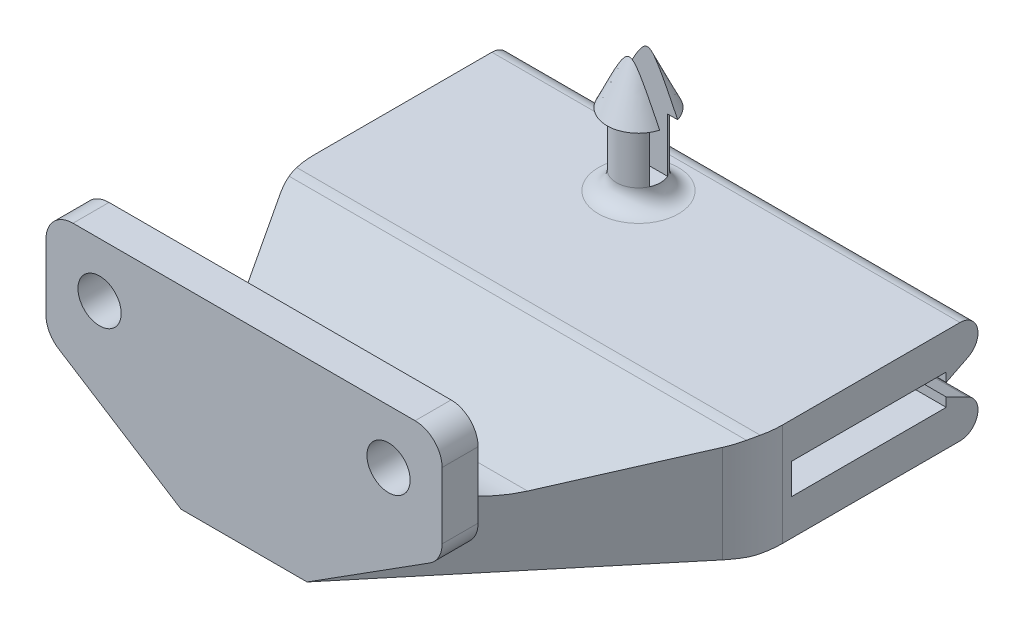
SolidWorks part; units mm, degrees
note: The reader was unsure of these and kept them because the rebuilt part matched: shared geometry of "Sketch5<3>".
ref_plane "Front Plane" through (0, 0, 0) normal (0, 0, 1) x (1, 0, 0)
ref_plane "Top Plane" through (0, 0, 0) normal (0, 1, 0) x (1, 0, 0)
ref_plane "Right Plane" through (0, 0, 0) normal (1, 0, 0) x (0, 0, -1)
sketch "Sketch1" plane through (0, 0, 0) normal (0, 1, 0) x (1, 0, 0)
  line L1 (-13, 5) -> (13, 5)
  line L2 (-13, 5) -> (-13, -5)
  line L3 (-13, -5) -> (13, -5)
  line L4 (13, 5) -> (13, -5)
  line L5 (-13, 5) -> (13, -5) construction
  line L6 (-13, -5) -> (13, 5) construction
  point P0 (0, 0)
sketch "Sketch2" plane through (0, 0, 0) normal (0, 1, 0) x (1, 0, 0)
  line L1 (-13, 7) -> (13, 7)
  line L2 (-13, 7) -> (-13, -7)
  line L3 (-13, -7) -> (13, -7)
  line L4 (13, 7) -> (13, -7)
  line L5 (-13, 7) -> (13, -7) construction
  line L6 (-13, -7) -> (13, 7) construction
  point P0 (0, 0)
extrude "Boss-Extrude1" add sketch "Sketch2" along normal blind 2
sketch "Sketch3" plane through (0, 0, 0) normal (0, -1, 0) x (1, 0, 0)
  line L4 (13, -7) -> (13, 7)
  line L5 (13, 7) -> (-13, 7)
  line L6 (-13, 7) -> (-13, -7)
  line L7 (-13, -7) -> (13, -7)
  line L8 (13, -7) -> (13, 7)
  line L9 (13, 7) -> (-13, 7)
  line L10 (-13, 7) -> (-13, -7)
  line L11 (-13, -7) -> (13, -7)
  dimension "D1" = 0
extrude "Boss-Extrude2" add sketch "Sketch3" along normal blind 2 from offset 1.7 separate body
sketch "Sketch4" plane through (0, 0, 0) normal (0, -1, 0) x (1, 0, 0)
  line L1 (-13, 7) -> (13, 7)
  line L2 (-13, 7) -> (-13, 3.1)
  line L3 (-13, 3.1) -> (13, 3.1)
  line L4 (13, 7) -> (13, 3.1)
extrude "Boss-Extrude3" add sketch "Sketch4" along normal blind 2
sketch "Sketch5" plane through (-13, 0, 0) normal (-1, 0, 0) x (0, 0, 1)
  line L0 (-5, 0) -> (-5, -0.5)
  line L3 (5, 0) -> (-5, 0) construction
  line L5 (-5, 0) -> (5, 0) construction
  line L7 (-5, -1.7) -> (-5, -1.2)
  line L9 (3.1, -1.7) -> (-7, -1.7) construction
  line L10 (-5, -0.5) -> (-10, 2)
  line L11 (-10, 2) -> (-5, 2)
  line L12 (-7, 2) -> (7, 2) construction
  line L13 (-5, 2) -> (-5, 0)
  line L14 (-5, -1.7) -> (-5, -3.7)
  line L15 (7, -3.7) -> (-7, -3.7) construction
  line L16 (-5, -3.7) -> (-10, -3.7)
  line L17 (-10, -3.7) -> (-5, -1.2)
  line L18 (-10, 2) -> (-10, -3.7)
  line L19 (-5, -1.2) -> (-5, -0.5)
  line M11 (-7, 2) -> (-7, 0)
  line M12 (-7, 0) -> (3.1, 0)
  line M14 (3.1, -1.7) -> (-7, -1.7)
  line M15 (-7, -1.7) -> (-7, -3.7)
extrude "Cut-Extrude2" cut sketch "Sketch5" against normal blind 233 contours L17 L19 L10 L18 M12 M11 M15 M14 | L10 M12 M11 | L17 M15 M14
extrude "Boss-Extrude4" add sketch "Sketch5<3>" against normal up to surface (26 mm away) contours L17 L7 M14 | L17 L16 M15 | L10 L0 M12 | L11 L10 M11 up to face at (13, -0.85, -1.98)
sketch "Sketch5<3>" plane through (-13, 0, 0) normal (-1, 0, 0) x (0, 0, 1) same geometry as "Sketch5"
fillet "Fillet1" radius 1 2 edges at (0, -3.7, -10) (0, 2, -10)
sketch "Sketch10" plane through (0, 0, 7) normal (0, 0, 1) x (1, 0, 0)
  line L4 (-13, -3.7) -> (13, -3.7)
  line L5 (13, -3.7) -> (13, 2)
  line L6 (13, 2) -> (-13, 2)
  line L7 (-13, 2) -> (-13, -3.7)
  line L8 (-13, -3.7) -> (13, -3.7)
  line L9 (13, -3.7) -> (13, 2)
  line L10 (13, 2) -> (-13, 2)
  line L11 (-13, 2) -> (-13, -3.7)
  dimension "D1" = 0
extrude "Cut-Extrude4" cut sketch "Sketch10" against normal blind 1.5
sketch3d "3DSketch1" plane through (0, 0, 0) normal (0, 0, 1) x (1, 0, 0)
sketch "Sketch8" plane through (0, 0, 21) normal (0, 0, 1) x (1, 0, 0)
  line L0 (0, -3.7) -> (0, 2) construction
  line L3 (-13, -0.85) -> (13, -0.85) construction
  line L7 (-3.5, 0.15) -> (3.5, 0.15)
  line L8 (-3.5, 0.15) -> (-3.5, -1.85)
  line L9 (-3.5, -1.85) -> (3.5, -1.85)
  line L10 (3.5, 0.15) -> (3.5, -1.85)
  line L11 (-3.5, 0.15) -> (3.5, -1.85) construction
  line L12 (-3.5, -1.85) -> (3.5, 0.15) construction
  point P12 (0, -0.85)
loft "Loft1" add profiles "Sketch8" section face at (0, -0.85, 5.5) section "Sketch8" connector at (13, 2, 5.5) connector at (3.5, 0.15, 21)
sketch "Sketch9" plane through (0, 0, 21) normal (0, 0, 1) x (1, 0, 0)
  line L0 (0, 8.9074) -> (0, 5.9074) construction
  line L1 (-8.025, 5.9074) -> (8.025, 5.9074) construction
  line L2 (-9.5, 8.9074) -> (9.5, 8.9074)
  line L3 (-11, 7.4074) -> (-11, 3.7322)
  line L4 (-10.3035, 2.4655) -> (-3.5, -1.85)
  line L5 (-3.5, -1.85) -> (3.5, -1.85)
  line L6 (11, 7.4074) -> (11, 3.7322)
  line L7 (10.3035, 2.4655) -> (3.5, -1.85)
  line L8 (-3.5, -1.85) -> (3.5, -1.85)
  line L9 (3.5, -1.85) -> (-3.5, -1.85)
  line L10 (-3.5, -1.85) -> (3.5, -1.85) construction
  line L11 (-3.5, -1.85) -> (3.5, -1.85)
  circle A0 centre (-8.025, 5.9074) radius 1.2
  circle A1 centre (8.025, 5.9074) radius 1.2
  arc A2 (11, 3.7322) -> (10.3035, 2.4655) centre (9.5, 3.7322) cw
  arc A3 (9.5, 8.9074) -> (11, 7.4074) centre (9.5, 7.4074) cw
  arc A4 (-9.5, 8.9074) -> (-11, 7.4074) centre (-9.5, 7.4074) ccw
  arc A5 (-11, 3.7322) -> (-10.3035, 2.4655) centre (-9.5, 3.7322) ccw
  point P5 (0, 5.9074)
  point P12 (0, 8.9074)
  dimension "D1" = 1.5
extrude "Boss-Extrude5" add sketch "Sketch9" against normal blind 2
fillet "Fillet6" radius 5 1 edges at (0, 0.3887, 19)
sketch "Sketch12" plane through (0, 0, 3.1) normal (0, 0, -1) x (-1, 0, 0)
  line L4 (-13, -1.7) -> (13, -1.7)
  line L5 (13, -1.7) -> (13, 0)
  line L6 (13, 0) -> (-13, 0)
  line L7 (-13, 0) -> (-13, -1.7)
  line L8 (-13, -1.7) -> (13, -1.7)
  line L9 (13, -1.7) -> (13, 0)
  line L10 (13, 0) -> (-13, 0)
  line L11 (-13, 0) -> (-13, -1.7)
  dimension "D1" = 0
extrude "Cut-Extrude5" cut sketch "Sketch12" against normal blind 0.5
fillet "Fillet8" radius 5 4 edges at (13, -0.85, 5.5) (0, -3.7, 5.5) (-13, -0.85, 5.5) (0, 2, 5.5)
sketch "Sketch13" plane through (0, 2, 0) normal (0, 1, 0) x (1, 0, 0)
  circle A0 centre (-2.2678, 3.1743) radius 1.375 construction
  circle A1 centre (-2.2678, 3.1743) radius 1.375 construction
  circle A2 centre (-2.2678, 3.1743) radius 1.225
extrude "Boss-Extrude6" add sketch "Sketch13" along normal blind 4
fillet "Fillet9" radius 1 1 edges at (-2.2678, 2, -1.9493)
sketch "Sketch14" plane through (0, 6, 0) normal (0, 1, 0) x (1, 0, 0)
  circle A0 centre (-2.2678, 3.1743) radius 1.75
extrude "Boss-Extrude7" add sketch "Sketch14" along normal blind 10 draft 25
sketch "Sketch15" plane through (0, 2, 0) normal (0, 1, 0) x (1, 0, 0)
  line L1 (-4.7678, 3.6743) -> (0.2322, 3.6743)
  line L2 (-4.7678, 3.6743) -> (-4.7678, 2.6743)
  line L3 (-4.7678, 2.6743) -> (0.2322, 2.6743)
  line L4 (0.2322, 3.6743) -> (0.2322, 2.6743)
  line L5 (-4.7678, 3.6743) -> (0.2322, 2.6743) construction
  line L6 (-4.7678, 2.6743) -> (0.2322, 3.6743) construction
  point P0 (-2.2678, 3.1743)
extrude "Cut-Extrude6" cut sketch "Sketch15" along normal blind 10 from offset 1
